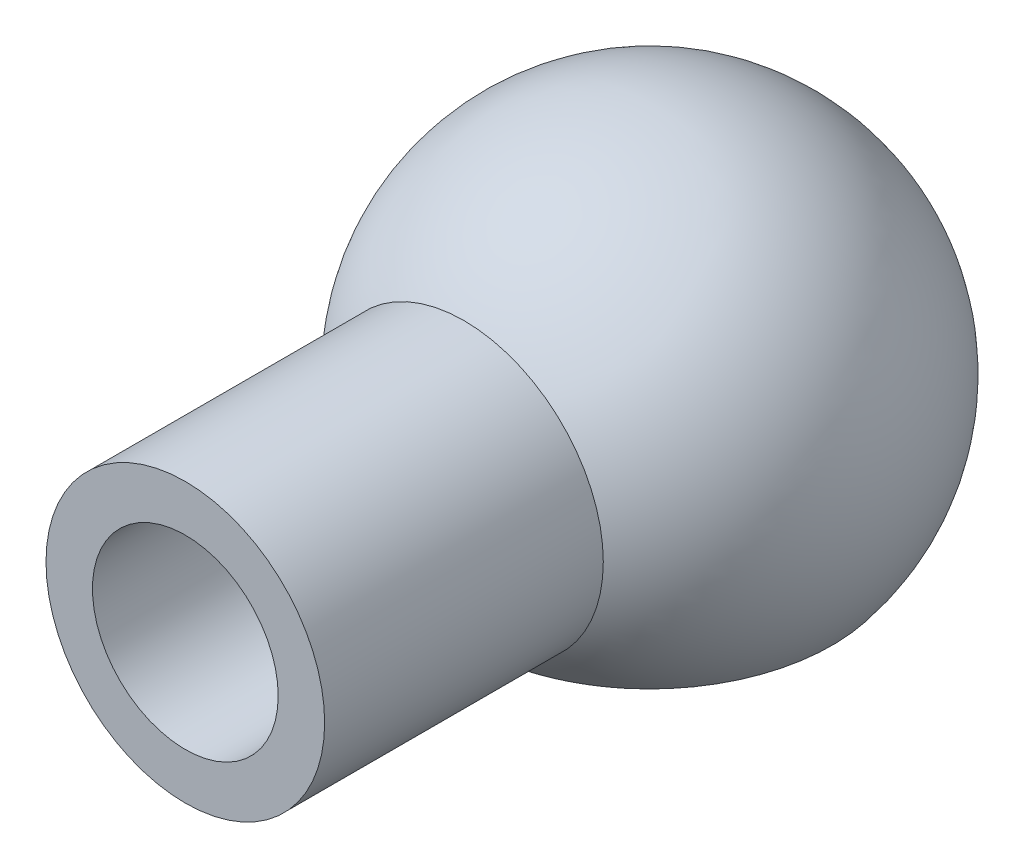
SolidWorks part; units mm, degrees
ref_plane "前视基准面" through (0, 0, 0) normal (0, 0, 1) x (1, 0, 0)
ref_plane "上视基准面" through (0, 0, 0) normal (0, 1, 0) x (1, 0, 0)
ref_plane "右视基准面" through (0, 0, 0) normal (1, 0, 0) x (0, 0, -1)
sketch "草图1" plane through (0, 0, 0) normal (0, 0, 1) x (1, 0, 0)
  circle A0 centre (0, 0) radius 6
  circle A1 centre (0, 0) radius 4
  dimension "D1" = 12
  dimension "D2" = 8
extrude "凸台-拉伸1" add sketch "草图1" along normal blind 20
sketch "草图2" plane through (0, 0, 0) normal (0, 1, 0) x (1, 0, 0)
  line L0 (0, 0) -> (0, 18.3774) construction
  line L1 (0, 10) -> (0, -10)
  arc A0 (0, 10) -> (0, -10) centre (0, 0) ccw
  dimension "D1" = 20
revolve "旋转3" add sketch "草图2" angle 360 about L0
sketch "草图3" plane through (0, 0, 20) normal (0, 0, 1) x (1, 0, 0)
  circle A0 centre (0, 0) radius 4
extrude "切除-拉伸2" cut sketch "草图3" against normal blind 12
sketch "草图4" plane through (0, 0, 0) normal (1, 0, 0) x (0, 0, -1)
  line L0 (0, 0) -> (0, 19.6414) construction
  line L1 (0, 7) -> (0, -7)
  line L2 (0, -7) -> (0, -10)
  line L3 (0, -10) -> (6, -10)
  line L5 (5.5, -4.3301) -> (7.8571, -6.1859)
  line L6 (7.8571, -6.1859) -> (6, -10)
  arc A0 (0, 7) -> (5.5, -4.3301) centre (0, 0) cw
  arc A1 (-8, -6) -> (-8, 6) centre (0, 0) ccw construction
  point P12 (5.4501, -4.3928)
  dimension "D1" = 7
  dimension "D2" = 3
  dimension "D3" = 5.5
revolve "切除-旋转1" cut sketch "草图4" angle 360 about L0 body kept at (-6, 0, 8)
